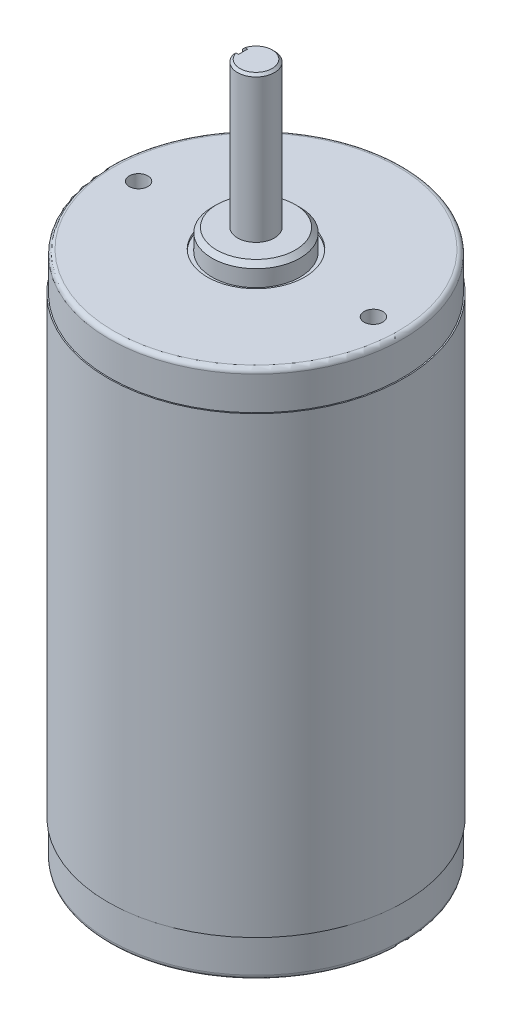
SolidWorks part; units mm, degrees
ref_plane "Front Plane" through (0, 0, 0) normal (0, 0, 1) x (1, 0, 0)
ref_plane "Top Plane" through (0, 0, 0) normal (0, 1, 0) x (1, 0, 0)
ref_plane "Right Plane" through (0, 0, 0) normal (1, 0, 0) x (0, 0, -1)
sketch "Sketch1" plane through (0, 0, 0) normal (0, 0, 1) x (1, 0, 0)
  line L0 (0, 0) -> (0, 181.9697) construction
  line L1 (10.5283, 119.3673) -> (10.5283, 118.8593)
  line L2 (10.5283, 118.8593) -> (9.525, 118.8593)
  line L3 (9.525, 118.8593) -> (9.525, 123.4313)
  line L4 (0, 0) -> (0, 154.9314)
  line L5 (9.525, 123.4313) -> (4, 123.4313)
  line L6 (4, 123.4313) -> (4, 154.9314)
  line L7 (4, 154.9314) -> (0, 154.9314)
  line L8 (32.004, 62.0649) -> (0, 62.0649) construction
  line L28 (0, 0) -> (15.0368, 0)
  line L29 (15.0368, 0) -> (15.0368, 4.7625)
  line L30 (15.0368, 4.7625) -> (31.75, 4.7625)
  line L31 (31.75, 4.7625) -> (31.75, 12.9921)
  line L32 (31.75, 12.9921) -> (32.004, 12.9921)
  line L33 (32.004, 12.9921) -> (32.004, 111.1377)
  line L34 (32.004, 111.1377) -> (31.75, 111.1377)
  line L35 (31.75, 111.1377) -> (31.75, 119.3673)
  line L41 (31.75, 119.3673) -> (10.5283, 119.3673)
  dimension "D4" = 64.008
  dimension "D13" = 62.0649
  dimension "D1" = 8
  dimension "D2" = 154.9314
  dimension "D3" = 30.0736
  dimension "D5" = 19.05
  dimension "D6" = 21.0566
  dimension "D7" = 0.508
  dimension "D8" = 4.064
  dimension "D9" = 0.254
  dimension "D10" = 63.5
  dimension "D11" = 114.6048
  dimension "D12" = 4.7625
  dimension "D14" = 98.1456
revolve "Revolve1" add sketch "Sketch1" angle 360 about L4
chamfer "Chamfer1" distance 1.0162 angle 45 1 edges at (0, 123.4313, -9.525)
fillet "Fillet1" radius 1 3 edges at (0, 119.3673, -31.75) (0, 4.7625, -31.75) (0, 0, -15.0368)
hole_wizard "A (0.234) Diameter Hole2" positions "Sketch3" profile "Sketch4" hole size "A" standard "Ansi (в дюймах)"
sketch "Sketch3" plane through (0, 119.3673, 0) normal (0, 1, 0) x (-1, 0, 0)
  line L0 (0, 0) -> (0, -20.2399) construction
  line L2 (23.6801, 0) -> (-25.6264, 0) construction
  point P0 (25.4, 0)
  point P1 (-25.4, 0)
  dimension "D1" = 25.4
sketch "Sketch4" plane through (-25.4, 119.3673, 0) normal (1, 0, 0) x (0, 0, 1)
  line L0 (0, 0) -> (0, 14.8277)
  line L1 (0, 14.8277) -> (2.0193, 13.6144)
  line L2 (2.0193, 13.6144) -> (2.0193, 0)
  line L5 (2.0193, 0) -> (0, 0)
  line L10 (0, 14.8277) -> (-2.0193, 13.6144) construction
  line L11 (0, -6.35) -> (0, 107.95) construction
  dimension "Диаметр отверстия" = 4.0386
  dimension "Глубина отверстия" = 13.6144
  dimension "Угол заточки сверла" = 118
sketch "Sketch5" plane through (0, 154.9314, 0) normal (0, 1, 0) x (1, 0, 0)
  line L0 (0, 0) -> (-5.7838, 0) construction
  line L2 (-4, -1) -> (-2.7999, -1)
  line L3 (-4, -1) -> (-4, 1)
  line L4 (-4, 1) -> (-2.7999, 1)
  line L5 (-2.7999, -1) -> (-2.7999, 1)
  circle A0 centre (0, 0) radius 4 construction
  dimension "D1" = 1.2001
  dimension "D2" = 2
extrude "Extrude1" cut sketch "Sketch5" against normal blind 29.8
fillet "Fillet2" radius 12.7 1 edges at (-2.7999, 125.1314, 0)
sketch "Sketch6" plane through (0, 4.7625, 0) normal (0, -1, 0) x (1, 0, 0)
  line L0 (0, 0) -> (-35.7085, 0) construction
  line L1 (0, 0) -> (-18.6071, 11.2074) construction
  circle A0 centre (-18.6071, 11.2074) radius 4.318
  dimension "D1" = 8.636
  dimension "D2" = 31.061
  dimension "D3" = 21.7216
extrude "Extrude2" add sketch "Sketch6" along normal blind 2.25 draft 45
ref_axis "Axis1" through (0, 111.1377, 0) along (0, -1, 0)
pattern_circular "CirPattern1" count 2 every 27.877 about axis through (0, 111.1377, 0) along (0, -1, 0) of "Extrude2" reverse direction yes
chamfer "Chamfer2" distance 0.508 angle 45 1 edges at (4, 154.9314, 0)
